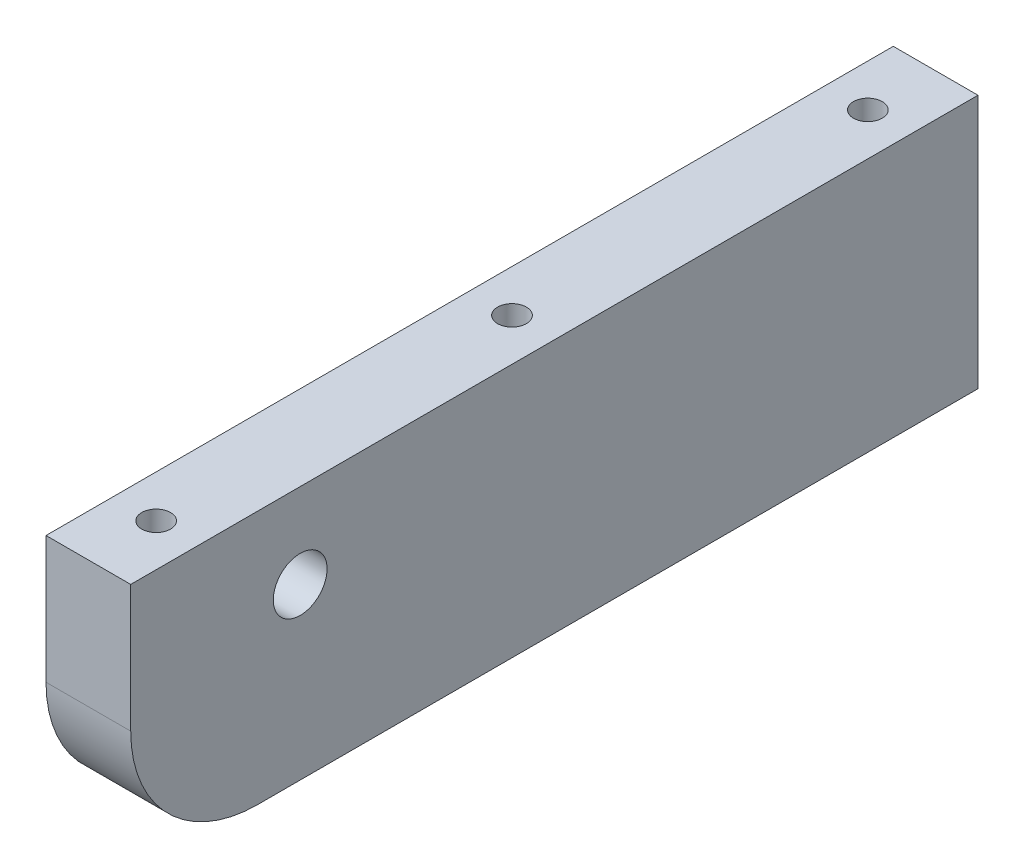
SolidWorks part; units mm, degrees
ref_plane "Front Plane" through (0, 0, 0) normal (0, 0, 1) x (1, 0, 0)
ref_plane "Top Plane" through (0, 0, 0) normal (0, 1, 0) x (1, 0, 0)
ref_plane "Right Plane" through (0, 0, 0) normal (1, 0, 0) x (0, 0, -1)
sketch "Sketch1" plane through (0, 0, 0) normal (1, 0, 0) x (0, 0, -1)
  line L1 (-50, -15) -> (50, -15)
  line L2 (-50, -15) -> (-50, 15)
  line L3 (-50, 15) -> (50, 15)
  line L4 (50, -15) -> (50, 15)
  line L5 (-50, -15) -> (50, 15) construction
  line L6 (-50, 15) -> (50, -15) construction
  circle A1 centre (-30, 5) radius 3.175
  point P0 (0, 0)
  dimension "D3" = 6.35
  dimension "D1" = 30
  dimension "D2" = 100
  dimension "D4" = 10
  dimension "D5" = 20
extrude "Boss-Extrude1" add sketch "Sketch1" along normal blind 10 contours L1 L4 L3 L2 region at (0, -0.0533, -0.3201)
fillet "Fillet1" radius 15 1 edges at (5, -15, 50)
hole_wizard "CBORE for M3 SHCS" positions "Sketch2" profile "Sketch3" counterbore size "M3" standard "ANSI Metric"
sketch "Sketch2" plane through (-616.2935, 25, -1323.2827) normal (0, 1, 0) x (1, 0, 0)
  line L3 (621.2935, -1281.2827) -> (621.2935, -1365.2827) construction
  line L5 (731.2935, -1281.2827) -> (731.2935, -1343.2827) construction
  circle A0 centre (731.2935, -1281.2827) radius 2.243
  circle A1 centre (731.2935, -1343.2827) radius 2.2384
  circle A3 centre (621.2935, -1281.2827) radius 2.3325
  circle A4 centre (621.2935, -1365.2827) radius 1.7576
  circle A5 centre (621.2935, -1323.2827) radius 1.8624
  circle A6 centre (731.2935, -1312.2827) radius 2.0271
  point P1 (731.2935, -1281.2827)
  point P8 (731.2935, -1343.2827)
  point P15 (621.2935, -1281.2827)
  point P17 (621.2935, -1365.2827)
  point P19 (621.2935, -1323.2827)
  point P27 (731.2935, -1312.2827)
sketch "Sketch3" plane through (115, 25, -42) normal (1, 0, 0) x (0, 0, 1)
  line L0 (0, 0) -> (0, 24.0215)
  line L1 (0, 24.0215) -> (1.7, 23)
  line L2 (1.7, 23) -> (1.7, 3)
  line L3 (1.7, 3) -> (3.25, 3)
  line L4 (3.25, 3) -> (3.25, 0)
  line L5 (3.25, 0) -> (0, 0)
  line L6 (0, 24.0215) -> (-1.7, 23) construction
  line L7 (0, -6.35) -> (0, 107.95) construction
  dimension "Hole Dia." = 3.4
  dimension "Hole Depth" = 23
  dimension "C'Bore Dia." = 6.5
  dimension "C'Bore Depth" = 3
  dimension "Drill Angle" = 118
